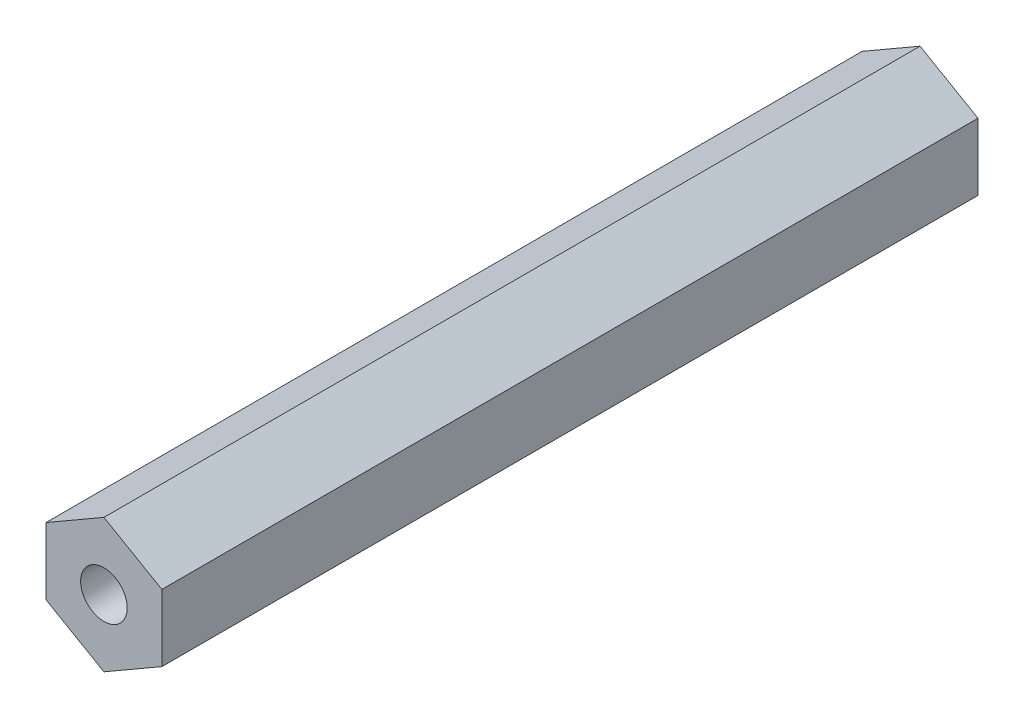
SolidWorks part; units mm, degrees
note: '?' marks a value the reader was unsure of.
ref_plane "Front" through (0, 0, 0) normal (0, 0, 1) x (1, 0, 0)
ref_plane "Top" through (0, 0, 0) normal (0, 1, 0) x (1, 0, 0)
ref_plane "Right" through (0, 0, 0) normal (1, 0, 0) x (0, 0, -1)
sketch "Sketch1" plane through (0, 0, 0) normal (0, 0, 1) x (1, 0, 0)
  line L1 (0, 7.3323) -> (-6.35, 3.6662)
  line L2 (-6.35, 3.6662) -> (-6.35, -3.6662)
  line L3 (-6.35, -3.6662) -> (0, -7.3323)
  line L4 (0, -7.3323) -> (6.35, -3.6662)
  line L5 (6.35, -3.6662) -> (6.35, 3.6662)
  line L6 (6.35, 3.6662) -> (0, 7.3323)
  circle A0 centre (0, 0) radius 6.35 construction
  dimension "Width" = 12.7
sketch "Sketch2" plane through (0, 0, 0) normal (1, 0, 0) x (0, 0, -1)
  line L0 (-44.737, 0) -> (44.737, 0) construction
  line L1 (-35.212, 7.3323) -> (-35.212, -7.3323) construction
  line L2 (35.212, 7.3323) -> (35.212, -7.3323) construction
  line L3 (-44.737, 7.3323) -> (-44.737, -7.3323) construction
  line L4 (44.737, 7.3323) -> (44.737, -7.3323) construction
  point P2 (-35.212, 0)
  point P4 (35.212, 0)
  dimension "Length" = 89.474
  dimension "D1" = 9.525
  dimension "D2" = 9.525
sketch "Sketch3" plane through (0, 0, 0) normal (0, 0, 1) x (1, 0, 0)
  line L0 (0, 7.3323) -> (-6.35, 3.6662) construction
  line L1 (-6.35, 3.6662) -> (-6.35, -3.6662) construction
  line L2 (-6.35, -3.6662) -> (0, -7.3323) construction
  line L3 (0, -7.3323) -> (6.35, -3.6662) construction
  line L4 (6.35, -3.6662) -> (6.35, 3.6662) construction
  line L5 (6.35, 3.6662) -> (0, 7.3323) construction
  line L6 (0, 7.3323) -> (-6.35, 3.6662)
  line L7 (-6.35, 3.6662) -> (-6.35, -3.6662)
  line L8 (-6.35, -3.6662) -> (0, -7.3323)
  line L9 (0, -7.3323) -> (6.35, -3.6662)
  line L10 (6.35, -3.6662) -> (6.35, 3.6662)
  line L11 (6.35, 3.6662) -> (0, 7.3323)
extrude "Boss-Extrude1" add sketch "Sketch3" along normal up to vertex (44.737 mm away) and the other way up to vertex (44.737 mm away) up to point (0, 0, 44.737) other way up to point (0, 0, -44.737)
ref_axis "Axis1" through (0, 0, 167.64) along (0, 0, -1)?
sketch "Sketch4" plane through (0, 0, 44.737) normal (0, 0, 1) x (1, 0, 0)
  circle A0 centre (0, 0) radius 6.35
  circle A1 centre (0, 0) radius 7.3323
  dimension "D1" = 12.7
extrude "Cut-Extrude1" [suppressed] cut sketch "Sketch4" against normal blind 12.7
mirror "Mirror1" [suppressed] about plane through (0, 0, 0) normal (0, 0, 1)
sketch "Sketch5" plane through (0, 0, 0) normal (0, 0, 1) x (1, 0, 0)
  circle A0 centre (0, 0) radius 69.85
  dimension "D1" = 139.7
ref_plane "Plane1" [suppressed] through (69.85, 0, 0) normal (1, 0, 0) x (0, 0, -1)
sketch "Sketch6" [suppressed] plane through (69.85, 0, 0) normal (1, 0, 0) x (0, 0, -1)
  line L0 (-11.1125, 0) -> (11.1125, 0)
  line L1 (-11.1125, 38.2905) -> (-11.1125, -76.581) construction
  line L2 (11.1125, -76.581) -> (11.1125, 38.2905) construction
surface "Surface-Sweep1" [suppressed]
hole_wizard "M3 Clearance Hole1" [suppressed] positions "Sketch7" profile "Sketch8" hole size "M3" standard "ANSI Metric"
sketch "Sketch7" plane through (0, 0, -44.737) normal (0, 0, -1) x (-1, 0, 0)
  point P0 (0, 0)
sketch "Sketch8" plane through (0, 0, -44.737) normal (1, 0, 0) x (0, 1, 0)
  line L0 (0, 0) -> (0, 89.474)
  line L1 (0, 89.474) -> (1.7, 89.474)
  line L2 (1.7, 89.474) -> (1.7, 0.025)
  line L3 (1.7, 0.025) -> (1.725, 0)
  line L5 (1.725, 0) -> (0, 0)
  line L6 (-1.7, 0.025) -> (-1.725, 0) construction
  line L11 (0, -6.35) -> (0, 107.95) construction
  dimension "Thru Hole Dia." = 3.4
  dimension "Thru Hole Depth" = 89.474
  dimension "Near C'Sink Dia." = 3.45
  dimension "Near C'Sink Angle" = 90
sketch "Sketch10" plane through (0, 0, 44.737) normal (0, 0, 1) x (1, 0, 0)
  circle A0 centre (0, 0) radius 3.175
  dimension "D1" = 6.35
extrude "Boss-Extrude2" [suppressed] add sketch "Sketch10" along normal blind 21.59
hole_wizard "Tap Drill for 1/4-20 Tap1" positions "Sketch11" profile "Sketch12" hole size "1/4-20" standard "ANSI Inch"
sketch "Sketch11" plane through (0, 0, -44.737) normal (0, 0, -1) x (-1, 0, 0)
  point P0 (0, 0)
sketch "Sketch12" plane through (0, 0, -44.737) normal (1, 0, 0) x (0, 1, 0)
  line L0 (0, 0) -> (0, 20.5838)
  line L1 (0, 20.5838) -> (2.5527, 19.05)
  line L2 (2.5527, 19.05) -> (2.5527, 0)
  line L5 (2.5527, 0) -> (0, 0)
  line L10 (0, 20.5838) -> (-2.5527, 19.05) construction
  line L11 (0, -6.35) -> (0, 107.95) construction
  dimension "Hole Dia." = 5.1054
  dimension "Hole Depth" = 19.05
  dimension "Drill Angle" = 118
hole_wizard "Tap Drill for #8-32 Tap1" [suppressed] positions "Sketch13" profile "Sketch14" hole size "#8-32" standard "ANSI Inch"
sketch "Sketch13" [suppressed] plane through (0, 0, 66.327) normal (0, 0, 1) x (1, 0, 0)
  point P0 (0, 0)
sketch "Sketch14" plane through (0, 0, 66.327) normal (1, 0, 0) x (0, -1, 0)
  line L0 (0, 0) -> (0, 13.7378)
  line L1 (0, 13.7378) -> (1.7272, 12.7)
  line L2 (1.7272, 12.7) -> (1.7272, 0)
  line L5 (1.7272, 0) -> (0, 0)
  line L10 (0, 13.7378) -> (-1.7272, 12.7) construction
  line L11 (0, -6.35) -> (0, 107.95) construction
  dimension "Hole Dia." = 3.4544
  dimension "Hole Depth" = 12.7
  dimension "Drill Angle" = 118
hole_wizard "Tap Drill for 1/4-20 Tap2" positions "Sketch15" profile "Sketch16" hole size "1/4-20" standard "ANSI Inch"
sketch "Sketch15" plane through (0, 0, 44.737) normal (0, 0, 1) x (1, 0, 0)
  point P0 (0, 0)
sketch "Sketch16" plane through (0, 0, 44.737) normal (1, 0, 0) x (0, -1, 0)
  line L0 (0, 0) -> (0, 20.5838)
  line L1 (0, 20.5838) -> (2.5527, 19.05)
  line L2 (2.5527, 19.05) -> (2.5527, 0)
  line L5 (2.5527, 0) -> (0, 0)
  line L10 (0, 20.5838) -> (-2.5527, 19.05) construction
  line L11 (0, -6.35) -> (0, 107.95) construction
  dimension "Hole Dia." = 5.1054
  dimension "Hole Depth" = 19.05
  dimension "Drill Angle" = 118
equation "\"D2@Sketch2\"=\"D1@Sketch2\""
equation "\"D1@Sketch2\"=\"Width@Sketch1\"*.75"
